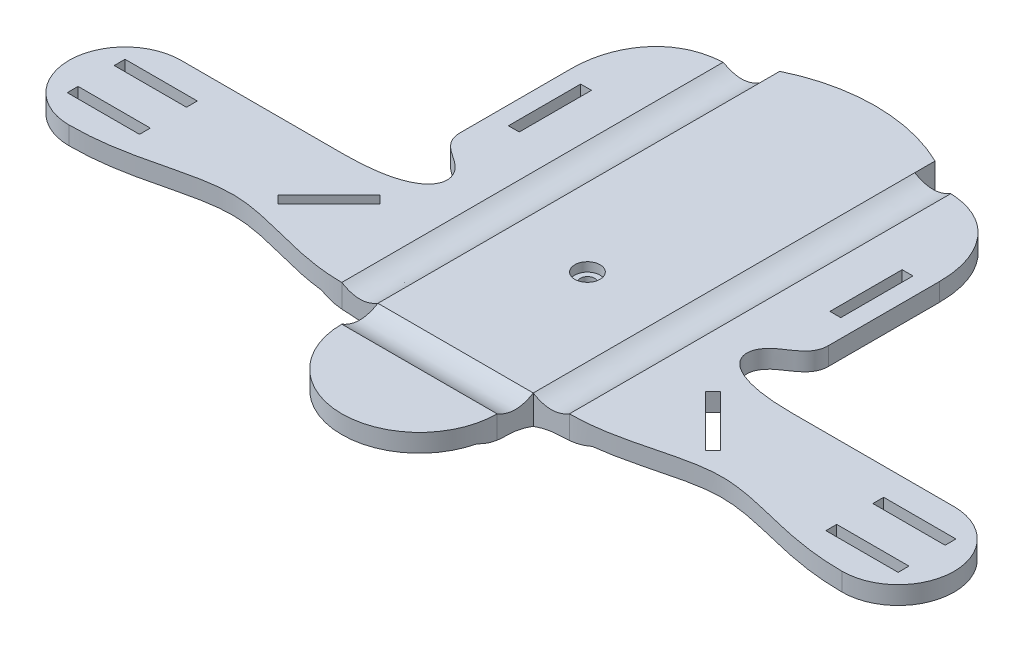
SolidWorks part; units mm, degrees
ref_plane "Front Plane" through (0, 0, 0) normal (0, 0, 1) x (1, 0, 0)
ref_plane "Top Plane" through (0, 0, 0) normal (0, 1, 0) x (1, 0, 0)
ref_plane "Right Plane" through (0, 0, 0) normal (1, 0, 0) x (0, 0, -1)
sketch "Foot Measurements" plane through (0, 0, 0) normal (0, 1, 0) x (1, 0, 0)
  line L0 (0, 0) -> (85, 0) construction
  line L1 (0, 0) -> (0, 145) construction
  line L2 (12.5, 115) -> (72.5, 115) construction
  line L3 (42.5, 145) -> (42.5, 115) construction
  line L4 (21, 83) -> (21, 0) construction
  line L5 (72.5, 115) -> (72.5, 0) construction
  line L6 (0, 145) -> (85, 145) construction
  line L7 (85, 145) -> (85, 0) construction
  line L8 (0, -100) -> (250, -100) construction
  line L9 (0, -100) -> (173, -100) construction
  line L11 (64, 0) -> (64, 83) construction
  line L12 (64, 83) -> (21, 83) construction
  line L13 (12.5, 115) -> (12.5, 0) construction
  dimension "D1" = 83
  dimension "D2" = 12.5
  dimension "D3" = 43
  dimension "D4" = 145
  dimension "D6" = 115
  dimension "D7" = 8.5
  dimension "D8" = 12.5
  dimension "D9" = 8.5
sketch "Sandal Design" plane through (0, 0, 0) normal (0, 1, 0) x (1, 0, 0)
  line L0 (42.5, 83) -> (42.5, 101.8434) construction
  line L1 (64, 83) -> (21, 83) construction
  line L2 (101.6421, 10) -> (103.7635, 12.1213)
  line L3 (157.5, 23.5018) -> (137.5, 23.5018)
  line L4 (157.5, 23.5018) -> (157.5, 20.5018)
  line L5 (0, 0) -> (85, 0) construction
  line L6 (137.5, 7.5018) -> (137.5, 10.5018)
  line L7 (-4.6213, 26.2635) -> (-2.5, 24.1421)
  line L8 (-4.6213, 26.2635) -> (-18.7635, 12.1213)
  line L9 (12.5, 105.6182) -> (21, 105.6182)
  line L10 (-64.5, 31.0018) -> (-19.5, 31.0018)
  line L11 (-2.5, 24.1421) -> (-16.6421, 10)
  line L12 (-52.5, 23.5018) -> (-52.5, 20.5018)
  line L13 (157.5, 10.5018) -> (137.5, 10.5018)
  line L14 (-72.5, 20.5018) -> (-52.5, 20.5018)
  line L15 (-72.5, 7.5018) -> (-52.5, 7.5018)
  line L16 (-72.5, 7.5018) -> (-72.5, 10.5018)
  line L17 (-72.5, 10.5018) -> (-52.5, 10.5018)
  line L18 (-52.5, 7.5018) -> (-52.5, 10.5018)
  line L19 (-72.5, 23.5018) -> (-72.5, 20.5018)
  line L20 (-72.5, 23.5018) -> (-52.5, 23.5018)
  line L21 (-16.6421, 10) -> (-18.7635, 12.1213)
  line L22 (157.5, 7.5018) -> (157.5, 10.5018)
  line L23 (12.5, 115) -> (12.5, 0) construction
  line L24 (157.5, 7.5018) -> (137.5, 7.5018)
  line L25 (64, 111.2308) -> (64, 105.6182)
  line L26 (72.5, 105.6182) -> (64, 105.6182)
  line L27 (93.5, 83) -> (93.5, 52.1918)
  line L29 (157.5, 20.5018) -> (137.5, 20.5018)
  line L30 (137.5, 23.5018) -> (137.5, 20.5018)
  line L32 (87.5, 24.1421) -> (101.6421, 10)
  line L38 (104.5, 31.0018) -> (149.5, 31.0018)
  line L39 (89.6213, 26.2635) -> (103.7635, 12.1213)
  line L40 (89.6213, 26.2635) -> (87.5, 24.1421)
  line L41 (11, 0) -> (21, 0)
  line L42 (21, 0) -> (21, -10)
  line L43 (64, 0) -> (64, -10)
  line L44 (64, 0) -> (74, 0)
  line L45 (21, 83) -> (21, 111.2308) construction
  line L46 (64, 83) -> (64, 111.2308) construction
  line L47 (-0.5, 80.6182) -> (-3.5, 80.6182)
  line L48 (-0.5, 80.6182) -> (-0.5, 60.6182)
  line L49 (-0.5, 60.6182) -> (-3.5, 60.6182)
  line L50 (-3.5, 80.6182) -> (-3.5, 60.6182)
  line L51 (-8.5, 83) -> (-8.5, 52.1918)
  line L54 (21, 111.2308) -> (21, 105.6182)
  line L57 (88.5, 80.6182) -> (88.5, 60.6182)
  line L58 (85.5, 60.6182) -> (88.5, 60.6182)
  line L59 (85.5, 80.6182) -> (85.5, 60.6182)
  line L60 (85.5, 80.6182) -> (88.5, 80.6182)
  arc A0 (149.5, 31.0018) -> (149.4998, 0.0018) centre (149.5, 15.5018) cw
  arc A1 (21, -10) -> (64, -10) centre (42.5, -10) ccw
  arc A4 (-64.5, 31.0018) -> (-64.4998, 0.0018) centre (-64.5, 15.5018) ccw
  arc A5 (64, 111.2308) -> (21, 111.2308) centre (42.5, 67) ccw
  spline S0 degree 3 poles (11, 0) (-2.4941, 0) (-26.3478, 12.0693) (-46.9264, 0.002) (-64.4998, 0.0018) knots 0 0 0 0 0.462856 1 1 1 1
  spline S1 degree 3 poles (-8.5, 52.1918) (-8.5, 47.5404) (4.8954, 43.2018) (1.7687, 31.0018) (-19.5, 31.0018) knots 0 0 0 0 0.331226 1 1 1 1
  spline S2 degree 3 poles (93.5, 83) (93.5, 91.1968) (88.2042, 102.2246) (77.5635, 105.6182) (72.5, 105.6182) knots 0 0 0 0 0.612936 1 1 1 1
  spline S3 degree 3 poles (74, 0) (87.4941, 0) (111.3478, 12.0693) (131.9264, 0.002) (149.4998, 0.0018) knots 0 0 0 0 0.462856 1 1 1 1
  spline S4 degree 3 poles (-8.5, 83) (-8.5, 91.1968) (-3.2042, 102.2246) (7.4365, 105.6182) (12.5, 105.6182) knots 0 0 0 0 0.612936 1 1 1 1
  spline S5 degree 3 poles (93.5, 52.1918) (93.5, 47.5404) (80.1046, 43.2018) (83.2313, 31.0018) (104.5, 31.0018) knots 0 0 0 0 0.331226 1 1 1 1
  dimension "D11" = 8
  dimension "D17" = 15
  dimension "D18" = 45
  dimension "D19" = 20
  dimension "D5" = 3
  dimension "D6" = 10
  dimension "D9" = 10
  dimension "D13" = 20
  dimension "D10" = 7.5
  dimension "D12" = 15.5
  dimension "D24" = 25
  dimension "D23" = 3
  dimension "D3" = 25
  dimension "D4" = 20
  dimension "D7" = 7.5
  dimension "D8" = 65
  dimension "D14" = 3
  dimension "D15" = 10
  dimension "D16" = 45
  dimension "D25" = 10
  dimension "D26" = 5
extrude "Boss-Extrude1" add sketch "Sandal Design" along normal blind 8
sketch "Sketch4" plane through (0, 0, 0) normal (0, -1, 0) x (1, 0, 0)
  line L0 (64, -15.5775) -> (64, -57.4225)
  line L1 (21, -15.5775) -> (21, -57.4225)
  arc A0 (21, -57.4225) -> (64, -57.4225) centre (42.5, -36.5) ccw
  arc A1 (64, -15.5775) -> (21, -15.5775) centre (42.5, -36.5) ccw
  dimension "D1" = 30
  dimension "D2" = 41.845
extrude "Boss-Extrude2" add sketch "Sketch4" along normal blind 2.5
sketch "Sketch6" plane through (0, -2.5, 0) normal (0, -1, 0) x (1, 0, 0)
  circle A0 centre (42.5, -36.5) radius 2
extrude "Cut-Extrude3" cut sketch "Sketch6" against normal up to next
sketch "Sketch7" plane through (0, 8, 0) normal (0, 1, 0) x (1, 0, 0)
  circle A0 centre (42.5, 36.5) radius 3.5
extrude "Cut-Extrude4" cut sketch "Sketch7" against normal blind 2.5
sketch "Sketch8" plane through (0, 0, 0) normal (0, 0, 1) x (1, 0, 0)
  line L0 (42.5, 8) -> (42.5, 0) construction
  line L2 (16, 8) -> (16, 6.5) construction
  line L3 (-80, 0) -> (21, 0)
  line L4 (11, 8) -> (21, 8) construction
  line L5 (11, 8) -> (21, 8)
  line L6 (64, 8) -> (21, 8) construction
  line L7 (5, 3) -> (21, 3) construction
  line L8 (5, 3) -> (-80, 3)
  line L9 (-80, 3) -> (-80, 0)
  line L10 (21, 8) -> (21, 0) construction
  line L11 (0, 0) -> (85, 0) construction
  line L13 (13, 3) -> (13, 1.5) construction
  line L15 (69, 8) -> (69, 6.5) construction
  line L16 (165, 3) -> (165, 0)
  line L17 (80, 3) -> (165, 3)
  line L18 (74, 8) -> (64, 8)
  line L19 (165, 0) -> (64, 0)
  spline S0 degree 2 poles (11, 8) (16, 5) (21, 8) knots 0 0 0 1 1 1
  spline S1 degree 2 poles (21, 0) (17, 1.5) (13, 1.5) knots 0 0 0 0.5 0.5 0.5
  spline S2 degree 3 poles (5, 3) (7.6685, 1.9993) (10.3371, 1.4993) (13.0056, 1.5) knots 0 0 0 0 0.50035 0.50035 0.50035 0.50035
  spline S3 degree 2 poles (64, 0) (68, 1.5) (72, 1.5) knots 0 0 0 0.5 0.5 0.5
  spline S4 degree 3 poles (80, 3) (77.3315, 1.9993) (74.6629, 1.4993) (71.9944, 1.5) knots 0 0 0 0 0.50035 0.50035 0.50035 0.50035
  spline S5 degree 2 poles (74, 8) (69, 5) (64, 8) knots 0 0 0 1 1 1
  dimension "D2" = 3
extrude "Cut-Extrude5" cut sketch "Sketch8" against normal through all both and the other way through all contours L3 L8 L9 | L19 L16 L17 | S5 L18 | L5 S0 region at (-33.328, 1.4484, 0) region at (16, 7.4, 0) region at (118.328, 1.4484, 0) region at (69, 7.4, 0)
sketch "Sketch9" plane through (0, 0, 0) normal (1, 0, 0) x (0, 0, -1)
  line L0 (-5, 8) -> (-5, 3) construction
  line L1 (-10, 8) -> (0, 8) construction
  line L2 (-15, 3) -> (0, 3) construction
  line L4 (-10, 8) -> (0.0018, 8)
  line L5 (-31.5, 0) -> (-31.5, 3)
  line L6 (-31.5, 8) -> (-31.5, 0) construction
  line L7 (-31.5, 3) -> (-15, 3)
  line L8 (-31.5, 0) -> (-10, 0) construction
  line L9 (-31.5, 0) -> (0, 0)
  line L10 (0, 8) -> (0, 0) construction
  spline S0 degree 2 poles (0, 0) (-3.75, 1.5) (-7.5, 1.5) knots 0 0 0 0.5 0.5 0.5
  spline S1 degree 2 poles (-10, 8) (-4.9993, 5) (0.0018, 8) knots 0 0 0 1 1 1
  spline S2 degree 3 poles (-15, 3) (-12.4982, 1.9993) (-9.9965, 1.4993) (-7.4947, 1.5) knots 0 0 0 0 0.50035 0.50035 0.50035 0.50035
  dimension "D2" = 1.5
  dimension "D3" = 3
extrude "Cut-Extrude6" cut sketch "Sketch9" against normal through all both and the other way through all contours L4 S1 | L9 S0 L7 L5 region at (0, 7.4, 4.9992) region at (0, 1.3125, 18.9141)
ref_plane "Plane1" through (42.5, 0, 0) normal (1, 0, 0) x (0, 0, -1)
sketch "Sketch12" plane through (42.5, 0, 0) normal (1, 0, 0) x (0, 0, -1)
  line L0 (36.5, -2.5) -> (36.5, 0) construction
  line L4 (57.4225, -2.5) -> (15.5775, -2.5) construction
  line L5 (0, 0) -> (145, 0) construction
  line L6 (34.5, 0) -> (34.5, -2.5)
  line L7 (34.5, 0) -> (15.5775, 0)
  line L8 (15.5775, 0) -> (6.5, -2.5)
  line L9 (6.5, -2.5) -> (34.5, -2.5)
  dimension "D1" = 2
revolve "Revolve1" add sketch "Sketch12" angle 360 about L0 region at (42.5, -1.3306, -22.623)
